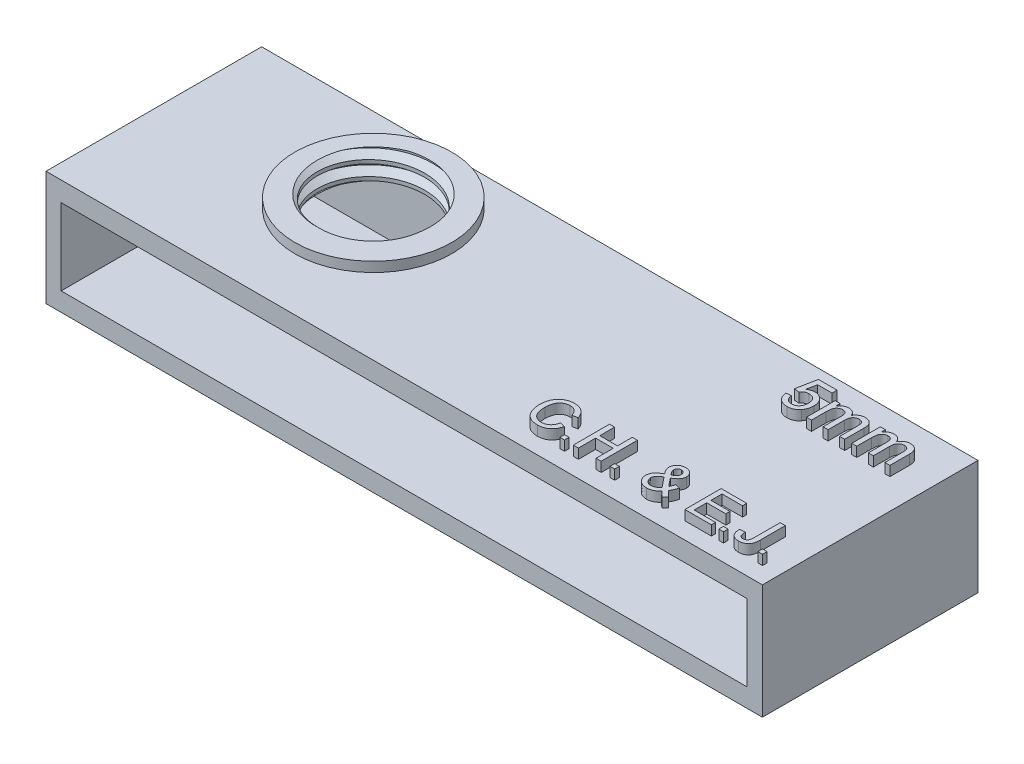
SolidWorks part; units mm, degrees
ref_plane "Ebene vorne" through (0, 0, 0) normal (0, 0, 1) x (1, 0, 0)
ref_plane "Ebene oben" through (0, 0, 0) normal (0, 1, 0) x (1, 0, 0)
ref_plane "Ebene rechts" through (0, 0, 0) normal (1, 0, 0) x (0, 0, -1)
sketch "Skizze1" plane through (0, 0, 0) normal (0, 1, 0) x (1, 0, 0)
  line L1 (-46.4165, 18.2033) -> (26.6835, 18.2033)
  line L2 (-46.4165, 18.2033) -> (-46.4165, -3.7967)
  line L3 (-46.4165, -3.7967) -> (26.6835, -3.7967)
  line L4 (26.6835, 18.2033) -> (26.6835, -3.7967)
  dimension "D1" = 73.1
  dimension "D2" = 22
extrude "Basis" add sketch "Skizze1" along normal blind 11.7
ref_plane "Ebene seitlich Handyschlitz" through (0, 0, 3.7967) normal (0, 0, 1) x (1, 0, 0)
sketch "Skizze2" plane through (0, 0, 3.7967) normal (0, 0, 1) x (1, 0, 0)
  line L1 (-44.8665, 9.7) -> (25.1335, 9.7)
  line L2 (-44.8665, 9.7) -> (-44.8665, 1.9)
  line L3 (-44.8665, 1.9) -> (25.1335, 1.9)
  line L4 (25.1335, 9.7) -> (25.1335, 1.9)
  line L5 (-46.4165, 11.7) -> (-46.4165, 0) construction
  line L6 (-46.4165, 11.7) -> (26.6835, 11.7) construction
  dimension "D1" = 70
  dimension "D2" = 7.8
  dimension "D3" = 2
  dimension "D4" = 1.55
extrude "Handyschlitz" cut sketch "Skizze2" against normal blind 21.25
ref_plane "Ebene oben auf Basis für Zylinder" through (0, 11.7, 0) normal (0, 1, 0) x (1, 0, 0)
sketch "Skizze3" plane through (0, 11.7, 0) normal (0, 1, 0) x (1, 0, 0)
  line L0 (-46.4165, 18.2033) -> (-46.4165, -3.7967) construction
  line L1 (26.6835, 18.2033) -> (-46.4165, 18.2033) construction
  circle A0 centre (-26.4165, 9.6033) radius 6.3
  dimension "D1" = 20
  dimension "D2" = 8.6
extrude "Zylinder" add sketch "Skizze3" along normal blind 1
ref_plane "Ebene oben auf Zylinder" through (0, 12.7, 0) normal (0, 1, 0) x (1, 0, 0)
sketch "Skizze6" plane through (0, 11.7, 0) normal (0, 1, 0) x (1, 0, 0)
  circle A0 centre (-26.4165, 9.6033) radius 8
extrude "Aufsatz-Linear austragen1" add sketch "Skizze6" along normal blind 1 contours A0
sketch "Skizze8" plane through (0, 12.7, 0) normal (0, 1, 0) x (1, 0, 0)
  circle A0 centre (-26.4165, 9.6033) radius 6.3
  dimension "D1" = 12.6
extrude "Schnitt-Linear austragen2" cut sketch "Skizze8" against normal blind 6
ref_plane "Ebene3" through (0, 9.7, 0) normal (0, -1, 0) x (-1, 0, 0)
sketch "Skizze12" plane through (0, 12.7, 0) normal (0, 1, 0) x (1, 0, 0)
  circle A0 centre (-26.4165, 9.6033) radius 7.5
thread "Gewinde2" pitch 1.5 method extrude profile "Gewindeprofil2" start angle 0, offset 1.6, length 8, pitch 1.5, diameter 12.6
ref_plane "Ebene5" through (-32.7165, 14.3, -9.6033) normal (0, 0, 1) x (-1, 0, 0)
sketch "Gewindeprofil2" plane through (-32.7165, 14.3, -9.6033) normal (0, 0, 1) x (-1, 0, 0)
  line L0 (0, 0) -> (0, 1.5) construction
  line L11 (0, 0) -> (0, 1.3125)
  line L12 (0, 1.3125) -> (-0.8119, 0.8437)
  line L13 (-0.8119, 0.8437) -> (-0.8119, 0.4687)
  line L15 (-0.8119, 0.4687) -> (0, 0)
  line L17 (-0.8119, 0.6562) -> (0, 0.6562) construction
  point P2 (0, 0)
  dimension "Pitch" = 1.5
  dimension "Profile_Angle" = 60
  dimension "Profile_Land" = 0.375
  dimension "Profile_Height" = 0.8119
extrude "Schnitt-Linear austragen5" cut sketch "Skizze12" along normal blind 6 contours A0
sketch "Skizze17" plane through (0, 9.7, 0) normal (0, -1, 0) x (-1, 0, 0)
  line L1 (13.3814, 0) -> (43.6823, 0)
  line L2 (13.3814, 0) -> (13.3814, 16.2694)
  line L3 (13.3814, 16.2694) -> (43.6823, 16.2694)
  line L4 (43.6823, 0) -> (43.6823, 16.2694)
extrude "Schnitt-Linear austragen7" cut sketch "Skizze17" along normal blind 6
ref_plane "Ebene für Logo" through (0, 0, 0) normal (0, -1, 0) x (-1, 0, 0)
sketch "Skizze24" plane through (0, 0, 0) normal (0, -1, 0) x (-1, 0, 0)
  line L1 (33.7615, 1.4341) -> (32.0294, -1.5659)
  line L2 (32.0294, -1.5659) -> (35.4935, -1.5659)
  line L3 (35.4935, -1.5659) -> (33.7615, 1.4341)
  line L4 (35.9478, -1.5381) -> (37.6798, 1.4619)
  line L5 (37.6798, 1.4619) -> (34.2157, 1.4619)
  line L6 (34.2157, 1.4619) -> (35.9478, -1.5381)
  line L7 (38.0931, 1.4341) -> (36.3611, -1.5659)
  line L8 (36.3611, -1.5659) -> (39.8252, -1.5659)
  line L9 (39.8252, -1.5659) -> (38.0931, 1.4341)
  line L10 (40.2382, -1.5381) -> (41.9702, 1.4619)
  line L11 (41.9702, 1.4619) -> (38.5061, 1.4619)
  line L12 (38.5061, 1.4619) -> (40.2382, -1.5381)
  line L13 (42.3422, 1.4341) -> (40.6101, -1.5659)
  line L14 (40.6101, -1.5659) -> (44.0742, -1.5659)
  line L15 (44.0742, -1.5659) -> (42.3422, 1.4341)
  line L16 (35.9475, 4.8546) -> (34.2154, 1.8546)
  line L17 (34.2154, 1.8546) -> (37.6795, 1.8546)
  line L18 (37.6795, 1.8546) -> (35.9475, 4.8546)
  line L19 (38.1338, 1.9341) -> (39.8658, 4.9341)
  line L20 (39.8658, 4.9341) -> (36.4017, 4.9341)
  line L21 (36.4017, 4.9341) -> (38.1338, 1.9341)
  line L22 (40.2791, 4.8546) -> (38.547, 1.8546)
  line L23 (38.547, 1.8546) -> (42.0111, 1.8546)
  line L24 (42.0111, 1.8546) -> (40.2791, 4.8546)
  line L28 (38.1338, 8.3316) -> (36.4017, 5.3316)
  line L29 (36.4017, 5.3316) -> (39.8658, 5.3316)
  line L30 (39.8658, 5.3316) -> (38.1338, 8.3316)
  circle A0 centre (33.7615, -0.5659) radius 1 construction
  circle A1 centre (35.9478, 0.4619) radius 1 construction
  circle A2 centre (38.0931, -0.5659) radius 1 construction
  circle A3 centre (40.2382, 0.4619) radius 1 construction
  circle A4 centre (42.3422, -0.5659) radius 1 construction
  circle A5 centre (35.9475, 2.8546) radius 1 construction
  circle A6 centre (38.1338, 3.9341) radius 1 construction
  circle A7 centre (40.2791, 2.8546) radius 1 construction
  circle A8 centre (38.1338, 6.3316) radius 1 construction
sketch "Skizze25" plane through (0, 0, 0) normal (0, -1, 0) x (-1, 0, 0)
  text T0 "EAH JENA         " font "Arial" height 3.5
extrude "EAH Jena" add sketch "Skizze25" along normal blind 1
extrude "LOGO" add sketch "Skizze24" along normal blind 1
ref_plane "Ebene für Schrift oben" through (0, 11.7, 0) normal (0, 1, 0) x (1, 0, 0)
sketch "Skizze26" plane through (0, 11.7, 0) normal (0, 1, 0) x (1, 0, 0)
  text T0 "C.H. & E.J." font "Arial" height 3.7
extrude "C.H. & E.J." add sketch "Skizze26" along normal blind 1
sketch "Skizze27" plane through (0, 11.7, 0) normal (0, 1, 0) x (1, 0, 0)
  text T0 "5mm" font "Arial" height 4
extrude "5mm" add sketch "Skizze27" along normal blind 1
